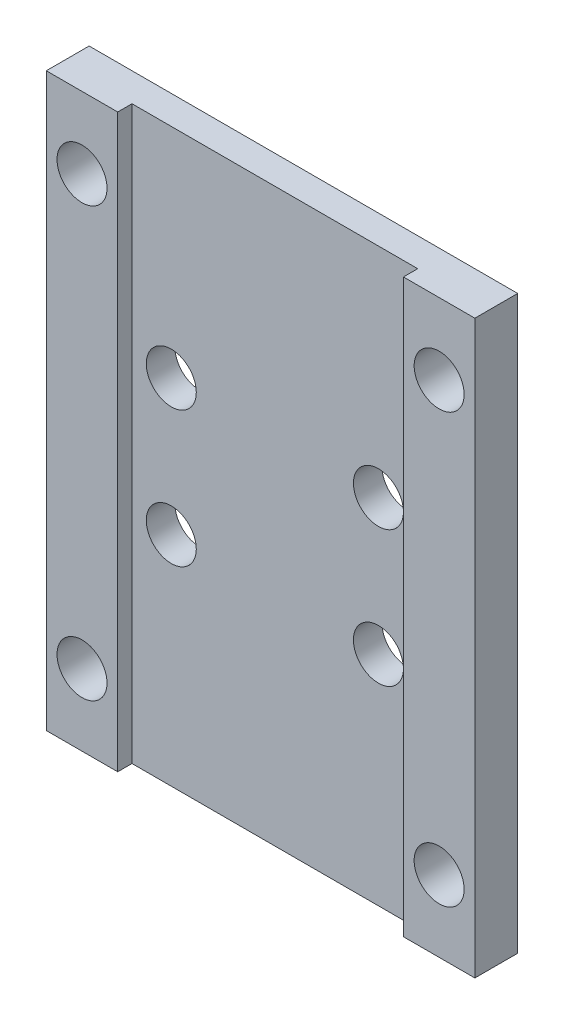
SolidWorks part; units mm, degrees
ref_plane "Plan de face" through (0, 0, 0) normal (0, 0, 1) x (1, 0, 0)
ref_plane "Plan de dessus" through (0, 0, 0) normal (0, 1, 0) x (1, 0, 0)
ref_plane "Plan de droite" through (0, 0, 0) normal (1, 0, 0) x (0, 0, -1)
sketch "Esquisse1" plane through (0, 0, 0) normal (0, 0, 1) x (1, 0, 0)
  line L0 (-10, 20) -> (-10, -20)
  line L1 (7.25, -4.75) -> (-7.25, -4.75) construction
  line L2 (7.25, -4.75) -> (7.25, 4.75) construction
  line L3 (7.25, 4.75) -> (-7.25, 4.75) construction
  line L4 (-7.25, -4.75) -> (-7.25, 4.75) construction
  line L5 (7.25, -4.75) -> (-7.25, 4.75) construction
  line L6 (7.25, 4.75) -> (-7.25, -4.75) construction
  line L7 (-12.5, 15) -> (12.5, 15) construction
  line L8 (-12.5, 15) -> (-12.5, -15) construction
  line L9 (-12.5, -15) -> (12.5, -15) construction
  line L10 (12.5, 15) -> (12.5, -15) construction
  line L11 (-15, 20) -> (15, 20)
  line L12 (-15, 20) -> (-15, -20)
  line L13 (-15, -20) -> (15, -20)
  line L14 (15, 20) -> (15, -20)
  line L15 (10, -20) -> (10, 20)
  line L16 (-10, 0) -> (-15, 0) construction
  line L17 (10, 0) -> (15, 0) construction
  circle A0 centre (-7.25, 4.75) radius 1.75
  circle A1 centre (7.25, 4.75) radius 1.75
  circle A2 centre (7.25, -4.75) radius 1.75
  circle A3 centre (-7.25, -4.75) radius 1.75
  circle A4 centre (-12.5, 15) radius 1.75
  circle A5 centre (12.5, 15) radius 1.75
  circle A6 centre (-12.5, -15) radius 1.75
  circle A7 centre (12.5, -15) radius 1.75
  point P0 (0, 0)
  point P11 (0, 15)
  point P12 (0, 4.75)
  point P13 (-12.5, 0)
  point P23 (0, 20)
  point P24 (-15, 0)
  dimension "D5" = 3.5
  dimension "D1" = 25
  dimension "D2" = 30
  dimension "D3" = 9.5
  dimension "D4" = 14.5
  dimension "D6" = 40
  dimension "D7" = 30
  dimension "D8" = 5
extrude "Boss.-Extru.1" add sketch "Esquisse1" against normal blind 2 contours L12 L13 L0 L11 A6 A4 | L13 L15 L11 L0 A3 A2 A1 A0 | L15 L13 L14 L11 A7 A5 region at (0, 0, 0) region at (-12.5, 0, 0) region at (12.5, 0, 0)
extrude "Boss.-Extru.2" add sketch "Esquisse1<3>" along normal blind 1 contours L12 L13 L0 L11 A6 A4 | L15 L13 L14 L11 A7 A5 region at (-12.5, 0, 0) region at (12.5, 0, 0)
sketch "Esquisse1<3>" plane through (0, 0, 0) normal (0, 0, 1) x (1, 0, 0) same geometry as "Esquisse1"
